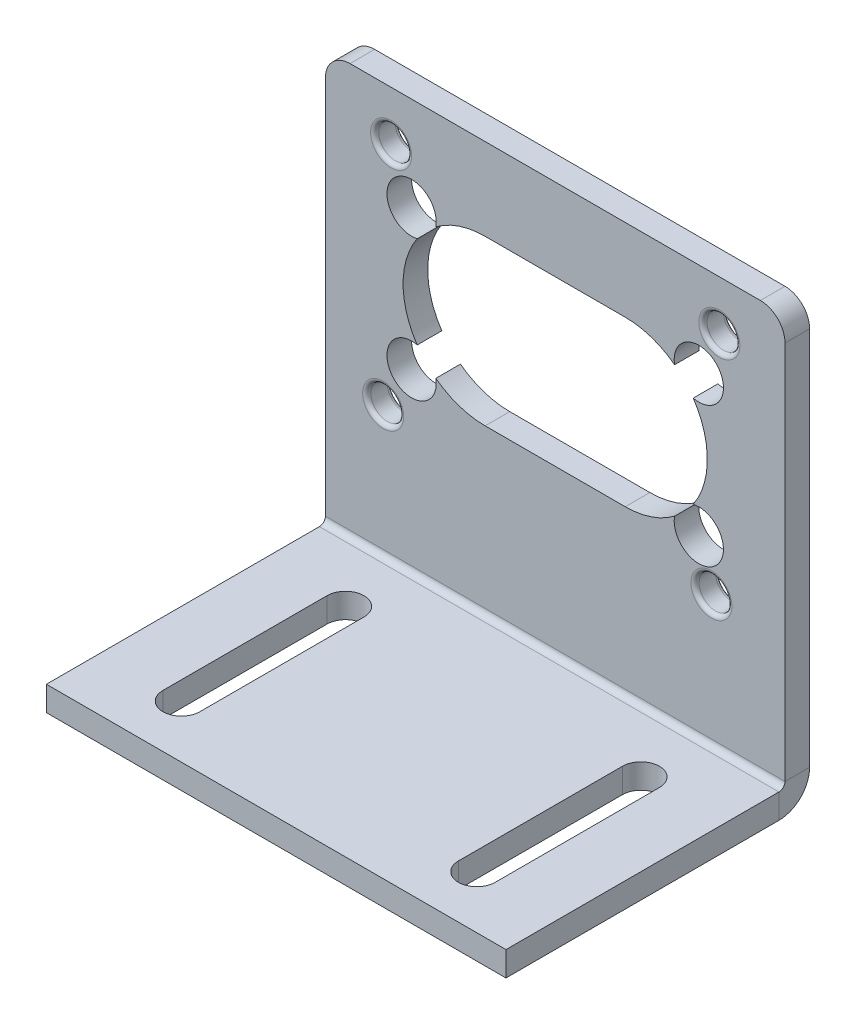
SolidWorks part; units mm, degrees
note: The reader was unsure of these and kept them because the rebuilt part matched: flange length of "边线-法兰2".
ref_plane "前视基准面" through (0, 0, 0) normal (0, 0, 1) x (1, 0, 0)
ref_plane "上视基准面" through (0, 0, 0) normal (0, 1, 0) x (1, 0, 0)
ref_plane "右视基准面" through (0, 0, 0) normal (1, 0, 0) x (0, 0, -1)
sketch "草图2" plane through (0, 0, 0) normal (0, 0, 1) x (1, 0, 0)
  line L0 (0, 0) -> (0, 66.4417) construction
  line L1 (25, -25) -> (-25, -25)
  line L2 (28, -22) -> (28, 22)
  line L3 (25, 25) -> (-25, 25)
  line L4 (-28, -22) -> (-28, 22)
  line L5 (28, -25) -> (-28, 25) construction
  line L6 (28, 25) -> (-28, -25) construction
  line L7 (0, 66.4417) -> (0, -60.1265) construction
  line L8 (0, 0) -> (-55.9163, 0) construction
  line L9 (-55.9163, 0) -> (66.1786, 0) construction
  line L10 (8.5344, 5) -> (8.5344, 31.2625) construction
  line L11 (8.5344, 31.2625) -> (8.5344, -18.8685) construction
  line L12 (-10.9826, 20.6558) -> (-10.9826, -17.716) construction
  line L13 (8.5344, 5) -> (-40.6898, 5) construction
  line L14 (-40.6898, 5) -> (52.6094, 5) construction
  line L15 (-8.5344, 15) -> (8.5344, 15)
  line L16 (-8.5344, -5) -> (8.5344, -5)
  line L17 (-28, -22) -> (-28, -25)
  line L18 (-28, -25) -> (-25, -25)
  line L19 (25, -25) -> (28, -25)
  line L20 (28, -25) -> (28, -22)
  circle A0 centre (-20, 19) radius 2
  arc A1 (28, 22) -> (25, 25) centre (25, 22) ccw
  arc A4 (-25, 25) -> (-28, 22) centre (-25, 22) ccw
  circle A5 centre (20, 19) radius 2
  circle A6 centre (-20.9659, -9) radius 2
  circle A7 centre (19.0341, -9) radius 2
  arc A8 (8.5344, 15) -> (14.5483, 12.9896) centre (8.5344, 5) cw
  arc A9 (-8.5344, 15) -> (-14.5483, 12.9896) centre (-8.5344, 5) ccw
  arc A10 (-16.8161, 10.6048) -> (-14.5483, 12.9896) centre (-17.5, 13.5258) cw
  arc A11 (16.8161, 10.6048) -> (14.5483, 12.9896) centre (17.5, 13.5258) ccw
  arc A12 (16.8161, -0.6048) -> (14.5483, -2.9896) centre (17.5, -3.5258) cw
  arc A13 (-16.8161, -0.6048) -> (-14.5483, -2.9896) centre (-17.5, -3.5258) ccw
  arc A14 (-16.8161, 10.6048) -> (-16.8161, -0.6048) centre (-8.5344, 5) ccw
  arc A15 (16.8161, 10.6048) -> (16.8161, -0.6048) centre (8.5344, 5) cw
  arc A16 (14.5483, -2.9896) -> (8.5344, -5) centre (8.5344, 5) cw
  arc A17 (-14.5483, -2.9896) -> (-8.5344, -5) centre (-8.5344, 5) ccw
  point P0 (0, 0)
  dimension "D3" = 4
  dimension "D4" = 3
  dimension "D8" = 28
  dimension "D10" = 10
  dimension "D13" = 3
  dimension "D14" = 35
  dimension "D1" = 50
  dimension "D2" = 56
  dimension "D6" = 44
  dimension "D7" = 20
  dimension "D9" = 40
  dimension "D11" = 14
  dimension "D12" = 20
base flange "基体-法兰1" sketch "草图2" thickness 3 reverse thickness direction no parameters "D1"=0.7366
fillet "圆角4" radius 0.5 8 edges at (21.0341, -9, -3) (-18.9659, -9, -3) (-18, 19, -3) (18, 19, -3) (-18.9659, -9, 0) (21.0341, -9, 0) (18, 19, 0) (-18, 19, 0)
edge flange "边线-法兰2" sketch "草图5" flange angle 90 flange length 34 flange position material outside bend radius 0.7366 thickness 3 relief rectangular parameters "D6"=10
sketch "草图5" plane through (0, -25, 0) normal (0, -1, 0) x (1, 0, 0)
  line L0 (-28, 0) -> (28, 0) construction
  line L1 (-28, 0) -> (28, 0)
  line L2 (-28, 0) -> (-28, 34)
  line L3 (-28, 34) -> (28, 34)
  line L4 (28, 34) -> (28, 0)
bend "边线折弯3" bend radius 0.7366 bend angle 90 parameters "D5"=1
sketch "草图6" plane through (0, -28, 0) normal (0, -1, 0) x (1, 0, 0)
  line L0 (-18, 27.5511) -> (-18, 7.5511) construction
  line L1 (-15.75, 27.5511) -> (-15.75, 7.5511)
  line L2 (-20.25, 27.5511) -> (-20.25, 7.5511)
  line L3 (18, 27.5511) -> (18, 7.5511) construction
  line L4 (20.25, 27.5511) -> (20.25, 7.5511)
  line L5 (15.75, 27.5511) -> (15.75, 7.5511)
  line L6 (0, 0) -> (0, 36.1909) construction
  arc A0 (-15.75, 27.5511) -> (-20.25, 27.5511) centre (-18, 27.5511) ccw
  arc A1 (-20.25, 7.5511) -> (-15.75, 7.5511) centre (-18, 7.5511) ccw
  arc A2 (20.25, 27.5511) -> (15.75, 27.5511) centre (18, 27.5511) ccw
  arc A3 (15.75, 7.5511) -> (20.25, 7.5511) centre (18, 7.5511) ccw
  point P2 (-18, 17.5511)
  point P7 (18, 17.5511)
  dimension "D4" = 2.25
  dimension "D5" = 2.25
  dimension "D1" = 20
  dimension "D2" = 20
  dimension "D3" = 36
extrude "切除-拉伸1" cut sketch "草图6" against normal through all normal cut yes
sketch "折弯-线1" plane through (0, 0, 0) normal (0, 1, 0) x (1, 0, 0)
sketch "边界框1" plane through (0, 0, 0) normal (0, 1, 0) x (1, 0, 0)
sheet metal parameters "钣金7" thickness 3 parameters "D1"=0.7366
flat pattern "平板型式7" [suppressed]
sketch "折弯-线2" plane through (0, 0, 0) normal (0, 1, 0) x (1, 0, 0)
sketch "边界框2" [suppressed] plane through (0, 0, 0) normal (0, 1, 0) x (1, 0, 0)
sheet metal parameters "钣金9" thickness 3 parameters "D1"=0.7366
flat pattern "平板型式7" [suppressed]
sketch "折弯-线2" plane through (0, 0, 0) normal (0, 1, 0) x (1, 0, 0)
sketch "边界框2" [suppressed] plane through (0, 0, 0) normal (0, 1, 0) x (1, 0, 0)
bend of the flat pattern "展开-<边线折弯3>1"
sheet metal parameters "钣金10" thickness 3 parameters "D1"=0.7366
flat pattern "平板型式7" [suppressed]
sketch "折弯-线2" plane through (0, 0, 0) normal (0, 1, 0) x (1, 0, 0)
sketch "边界框2" [suppressed] plane through (0, 0, 0) normal (0, 1, 0) x (1, 0, 0)
bend of the flat pattern "展开-<边线折弯3>1"
